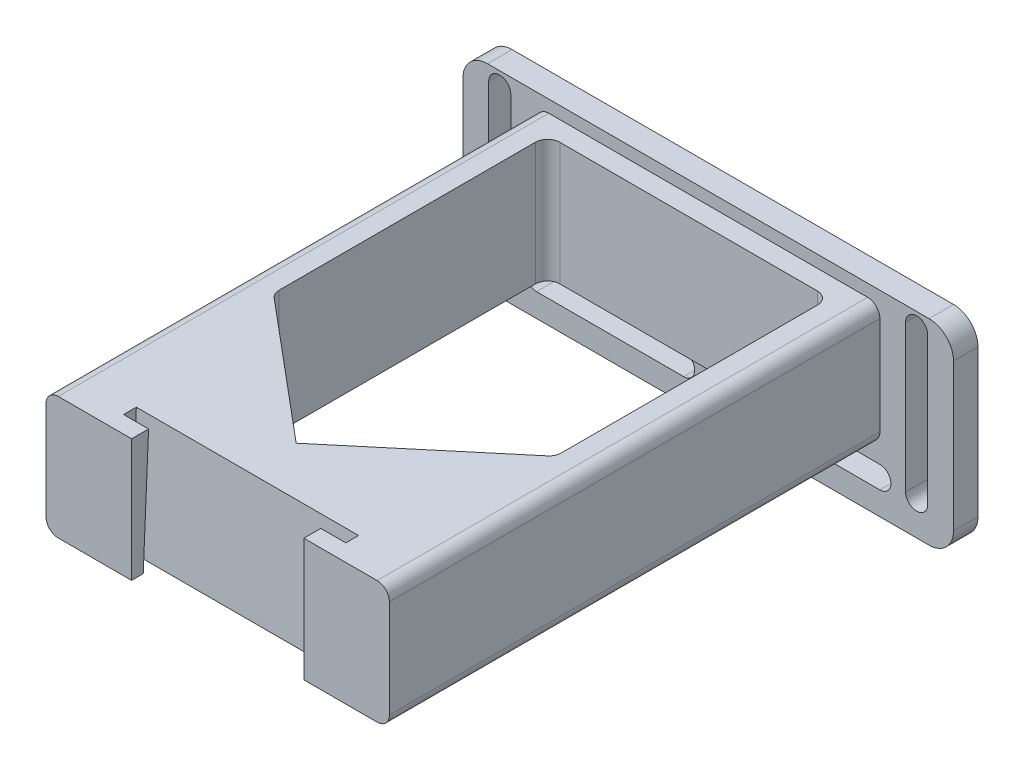
SolidWorks part; units mm, degrees
ref_plane "Front Plane" through (0, 0, 0) normal (0, 0, 1) x (1, 0, 0)
ref_plane "Top Plane" through (0, 0, 0) normal (0, 1, 0) x (1, 0, 0)
ref_plane "Right Plane" through (0, 0, 0) normal (1, 0, 0) x (0, 0, -1)
sketch "Sketch1" plane through (0, 0, 0) normal (0, 0, 1) x (1, 0, 0)
  line L1 (50, -20) -> (-50, -20)
  line L2 (50, -20) -> (50, 20)
  line L3 (50, 20) -> (-50, 20)
  line L4 (-50, -20) -> (-50, 20)
  line L5 (50, -20) -> (-50, 20) construction
  line L6 (50, 20) -> (-50, -20) construction
  point P0 (0, 0)
  dimension "D1" = 40
  dimension "D2" = 100
extrude "Boss-Extrude1" add sketch "Sketch1" along normal blind 5
sketch "Sketch2" plane through (0, 0, 5) normal (0, 0, 1) x (1, 0, 0)
  line L0 (-42.5, 17) -> (-42.5, -13) construction
  line L1 (-40.25, 17) -> (-40.25, -13)
  line L2 (-35, -13) -> (-5, -13) construction
  line L3 (-44.75, 17) -> (-44.75, -13)
  line L7 (42.5, 17) -> (42.5, -13) construction
  line L8 (44.75, 17) -> (44.75, -13)
  line L9 (40.25, 17) -> (40.25, -13)
  line L11 (5, -13) -> (35, -13) construction
  line L12 (5, -10.75) -> (35, -10.75)
  line L13 (5, -15.25) -> (35, -15.25)
  line L14 (-50, -20) -> (50, -20) construction
  line L15 (-50, 20) -> (-50, -20) construction
  line L16 (50, -20) -> (50, 20) construction
  line L17 (-35, -10.75) -> (-5, -10.75)
  line L18 (-35, -15.25) -> (-5, -15.25)
  arc A8 (-40.25, 17) -> (-44.75, 17) centre (-42.5, 17) ccw
  arc A9 (-44.75, -13) -> (-40.25, -13) centre (-42.5, -13) ccw
  arc A10 (44.75, 17) -> (40.25, 17) centre (42.5, 17) ccw
  arc A11 (40.25, -13) -> (44.75, -13) centre (42.5, -13) ccw
  arc A14 (5, -10.75) -> (5, -15.25) centre (5, -13) ccw
  arc A15 (35, -15.25) -> (35, -10.75) centre (35, -13) ccw
  arc A16 (-35, -10.75) -> (-35, -15.25) centre (-35, -13) ccw
  arc A17 (-5, -15.25) -> (-5, -10.75) centre (-5, -13) ccw
  point P2 (-42.5, 2)
  point P7 (-20, -13)
  point P10 (42.5, 2)
  point P21 (20, -13)
  dimension "D7" = 30
  dimension "D1" = 30
  dimension "D2" = 4.5
  dimension "D3" = 30
  dimension "D4" = 4.5
  dimension "D5" = 30
  dimension "D6" = 4.5
  dimension "D8" = 4.5
  dimension "D9" = 7
  dimension "D10" = 7
  dimension "D11" = 7.5
  dimension "D12" = 7.5
  dimension "D13" = 7.5
  dimension "D14" = 7.5
extrude "Cut-Extrude1" cut sketch "Sketch2" against normal blind 5 contours L1 A9 L3 A8
extrude "Cut-Extrude2" cut sketch "Sketch2<3>" against normal blind 5 contours L17 A17 L18 A16
sketch "Sketch2<3>" plane through (0, 0, 5) normal (0, 0, 1) x (1, 0, 0) same geometry as "Sketch2"
extrude "Cut-Extrude3" cut sketch "Sketch2<4>" against normal blind 5 contours L12 A15 L13 A14
sketch "Sketch2<4>" plane through (0, 0, 5) normal (0, 0, 1) x (1, 0, 0) same geometry as "Sketch2"
extrude "Cut-Extrude4" cut sketch "Sketch2<5>" against normal blind 5 contours L9 A11 L8 A10
sketch "Sketch2<5>" plane through (0, 0, 5) normal (0, 0, 1) x (1, 0, 0) same geometry as "Sketch2"
sketch "Sketch3" plane through (0, 0, 5) normal (0, 0, 1) x (1, 0, 0)
  line L0 (50, 20) -> (-50, 20) construction
  line L1 (35, -7.5) -> (-35, -7.5)
  line L2 (35, -7.5) -> (35, 17.5)
  line L3 (35, 17.5) -> (-35, 17.5)
  line L4 (-35, -7.5) -> (-35, 17.5)
  line L5 (35, -7.5) -> (-35, 17.5) construction
  line L6 (35, 17.5) -> (-35, -7.5) construction
  point P0 (0, 5)
  point P8 (0, 20)
  dimension "D1" = 25
  dimension "D2" = 70
  dimension "D3" = 2.5
extrude "Boss-Extrude2" add sketch "Sketch3" along normal blind 100
fillet "Fillet1" radius 5 4 edges at (-50, 20, 2.5) (50, 20, 2.5) (50, -20, 2.5) (-50, -20, 2.5)
fillet "Fillet2" radius 2.5 4 edges at (-35, 17.5, 55) (35, 17.5, 55) (35, -7.5, 55) (-35, -7.5, 55)
sketch "Sketch7" plane through (0, -7.5, 0) normal (0, -1, 0) x (1, 0, 0)
sketch "Sketch8" plane through (0, -7.5, 0) normal (0, -1, 0) x (1, 0, 0)
  line L0 (-28.75, 9) -> (28.75, 9)
  line L1 (28.75, 9) -> (28.75, 64.8759)
  line L2 (-28.75, 9) -> (-28.75, 64.8759)
  line L3 (-28.75, 64.8759) -> (0, 89)
  line L4 (0, 89) -> (28.75, 64.8759)
  line L5 (-32.5, 5) -> (32.5, 5) construction
  point P2 (0, 9)
  dimension "D1" = 50
  dimension "D2" = 4
  dimension "D3" = 80
  dimension "D4" = 57.5
extrude "Cut-Extrude8" cut sketch "Sketch8" against normal through all contours L2 L3 L4 L1 L0
fillet "Fillet3" radius 2.5 4 edges at (28.75, 5, 64.8759) (-28.75, 5, 64.8759) (28.75, 5, 9) (-28.75, 5, 9)
ref_plane "Plane1" through (0, 12.891, -0.5628) normal (0, 0.999, -0.0436) x (-1, 0, 0)
sketch "Sketch9" plane through (0, 12.891, -0.5628) normal (0, 0.999, -0.0436) x (-1, 0, 0)
  line L0 (17.55, 102.2034) -> (22.65, 102.2034)
  line L1 (-22.65, 102.2034) -> (-17.55, 102.2034)
  line L2 (-22.65, 102.2034) -> (-22.65, 99.6034)
  line L3 (-22.65, 99.6034) -> (22.65, 99.6034)
  line L4 (22.65, 102.2034) -> (22.65, 99.6034)
  line L5 (17.55, 102.2034) -> (17.55, 108.9053)
  line L6 (17.55, 108.9053) -> (-17.55, 108.9053)
  line L7 (-17.55, 102.2034) -> (-17.55, 108.9053)
  line L8 (-35, 105.5544) -> (-17.55, 105.5544) construction
  line L9 (35, 105.5544) -> (17.55, 105.5544) construction
  point P9 (-17.55, 105.5544)
  dimension "D1" = 5.1
  dimension "D2" = 35.1
extrude "Cut-Extrude9" cut sketch "Sketch9" against normal through all both and the other way through all contours L7 L6 L5 L0 L4 L3 L2 L1
